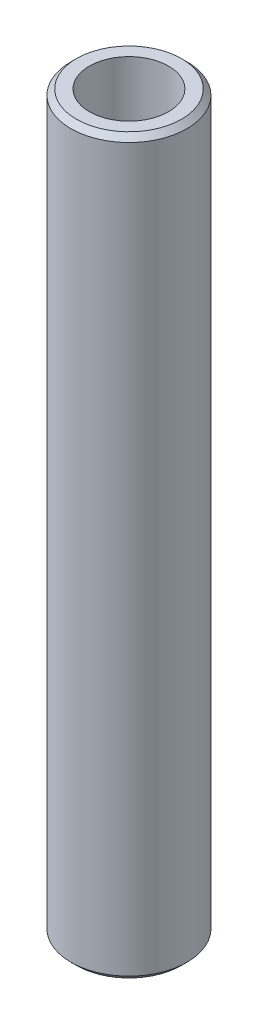
SolidWorks part; units mm, degrees
ref_plane "Front Plane" through (0, 0, 0) normal (0, 0, 1) x (1, 0, 0)
ref_plane "Top Plane" through (0, 0, 0) normal (0, 1, 0) x (1, 0, 0)
ref_plane "Right Plane" through (0, 0, 0) normal (1, 0, 0) x (0, 0, -1)
sketch "Sketch1" plane through (0, 0, 0) normal (0, 1, 0) x (1, 0, 0)
  circle A0 centre (0, 0) radius 47.5
  dimension "SHAFT_OD" = 95
extrude "Boss-Extrude1" add sketch "Sketch1" along normal blind 600
sketch "Sketch2" plane through (0, 0, 0) normal (0, 1, 0) x (1, 0, 0)
  circle A0 centre (0, 0) radius 32.4012
  dimension "BORE_D" = 64.8024
extrude "Cut-Extrude1" cut sketch "Sketch2" along normal through all
chamfer "Chamfer1" distance 4.4748 angle 45 2 edges at (0, 600, 47.5) (0, 0, 47.5)
